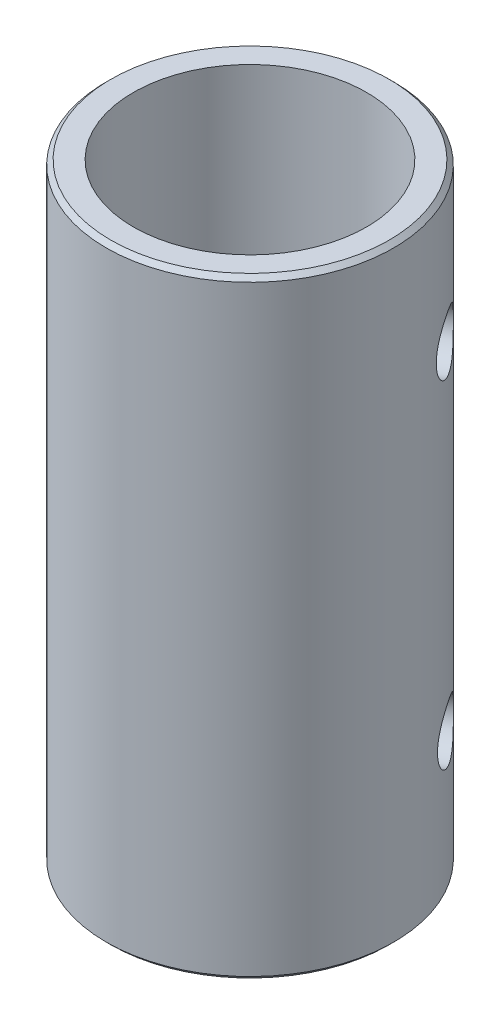
SolidWorks part; units mm, degrees
ref_plane "Front Plane" through (0, 0, 0) normal (0, 0, 1) x (1, 0, 0)
ref_plane "Top Plane" through (0, 0, 0) normal (0, 1, 0) x (1, 0, 0)
ref_plane "Right Plane" through (0, 0, 0) normal (1, 0, 0) x (0, 0, -1)
sketch "Sketch1" plane through (0, 0, 0) normal (0, 1, 0) x (1, 0, 0)
  circle A0 centre (0, 0) radius 7.94
  circle A1 centre (0, 0) radius 6.44
  dimension "D1" = 15.88
  dimension "D2" = 1.5
extrude "Boss-Extrude1" add sketch "Sketch1" along normal blind 33.7
chamfer "Chamfer1" distance 0.25 angle 45 2 edges at (0, 0, 7.94) (0, 33.7, 7.94)
sketch "Sketch2" plane through (-4.9275, 0, 3.1531) normal (-0.8423, 0, 0.539) x (0.539, 0, 0.8423)
  circle A0 centre (0, 26.2) radius 1.55 construction
  circle A1 centre (0, 26.2) radius 1.55
extrude "Cut-Extrude1" cut sketch "Sketch2" against normal through all both and the other way through all
sketch "Sketch3" plane through (-4.8783, 0, 3.2287) normal (-0.8339, 0, 0.5519) x (0.5519, 0, 0.8339)
  circle A0 centre (0, 7.5) radius 1.55 construction
  circle A1 centre (0, 7.5) radius 1.55
extrude "Cut-Extrude2" cut sketch "Sketch3" against normal through all both and the other way through all
